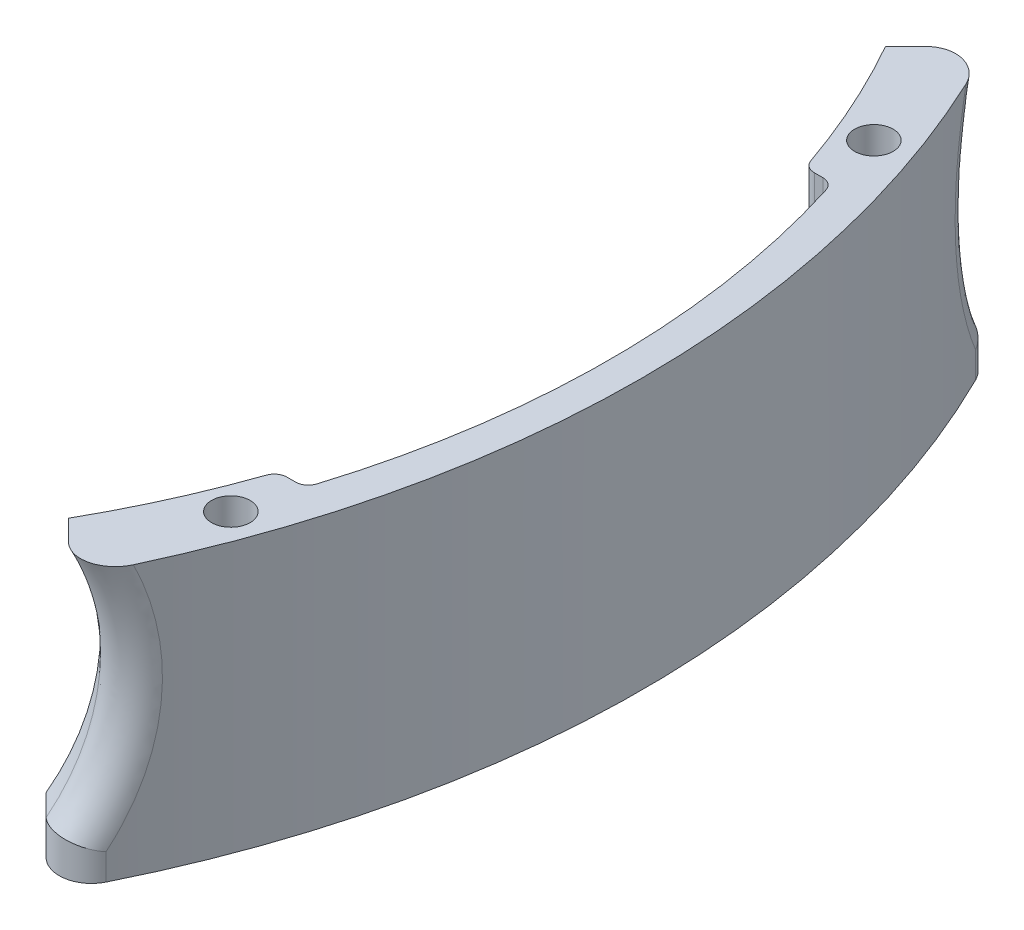
SolidWorks part; units mm, degrees
ref_plane "Front Plane" through (0, 0, 0) normal (0, 0, 1) x (1, 0, 0)
ref_plane "Top Plane" through (0, 0, 0) normal (0, 1, 0) x (1, 0, 0)
ref_plane "Right Plane" through (0, 0, 0) normal (1, 0, 0) x (0, 0, -1)
sketch "Sketch1" plane through (0, 0, 0) normal (0, 1, 0) x (1, 0, 0)
  line L0 (0, 0) -> (98.9949, 98.9949) construction
  line L1 (0, 0) -> (33.5233, 0) construction
  line L2 (0, 0) -> (98.9949, -98.9949) construction
  line L3 (119.0017, 73.7469) -> (65.7347, 20.4798) construction
  line L4 (74.0325, -28.7777) -> (119.0017, -73.7469) construction
  line L5 (119.0017, 73.7469) -> (110.9931, 65.7383)
  line L6 (119.0017, -73.7469) -> (110.9931, -65.7383)
  circle A0 centre (0, 0) radius 140 construction
  circle A1 centre (124, 50) radius 3
  circle A2 centre (124, -50) radius 3
  arc A3 (119.0017, 73.7469) -> (119.0017, -73.7469) centre (-14.6329, 0) cw
  arc A4 (110.9931, -65.7383) -> (110.9931, 65.7383) centre (0, 0) ccw
  arc A5 (115.544, 75.4559) -> (109.97, -83.3702) centre (0, 0) cw construction
  dimension "D5" = 280
  dimension "D8" = 6
  dimension "D10" = 2
  dimension "D11" = 129
  dimension "D1" = 45
  dimension "D2" = 45
  dimension "D3" = 32
  dimension "D4" = 32
  dimension "D6" = 50
  dimension "D7" = 50
  dimension "D9" = 124
extrude "Boss-Extrude1" add sketch "Sketch1" along normal blind 42
ref_plane "Plane1" through (96.3743, 0, 96.3743) normal (-0.7071, 0, -0.7071) x (0, -1, 0)
sketch "Sketch2" plane through (96.3743, 0, 96.3743) normal (-0.7071, 0, -0.7071) x (0, -1, 0)
  circle A0 centre (-26, 0) radius 38
  dimension "D1" = 76
  dimension "D2" = 26
extrude "Cut-Extrude1" cut sketch "Sketch2" along normal up to next
mirror "Mirror1" about plane through (0, 0, 0) normal (0, 0, 1) of "Cut-Extrude1"
fillet "Fillet1" radius 5 4 edges at (119.0017, 2.753, 73.7469) (121.517, 17.9624, 68.9928) (119.0017, 2.753, -73.7469) (121.517, 17.9624, -68.9928)
sketch "Sketch3" plane through (0, 42, 0) normal (0, 1, 0) x (1, 0, 0)
  line L0 (122.3111, 41) -> (122.3111, -41)
  line L1 (122.3111, -41) -> (126.5227, -41)
  line L2 (122.3111, 41) -> (126.5227, 41)
  arc A0 (112.2726, -63.5284) -> (112.2726, 63.5284) centre (0, 0) ccw construction
  arc A1 (126.5227, -41) -> (126.5227, 41) centre (0, 0) ccw
  dimension "D1" = 133
  dimension "D2" = 82
extrude "Cut-Extrude2" cut sketch "Sketch3" against normal up to next
fillet "Fillet2" radius 2 4 edges at (126.5227, 21, 41) (122.3111, 21, 41) (126.5227, 21, -41) (122.3111, 21, -41)
